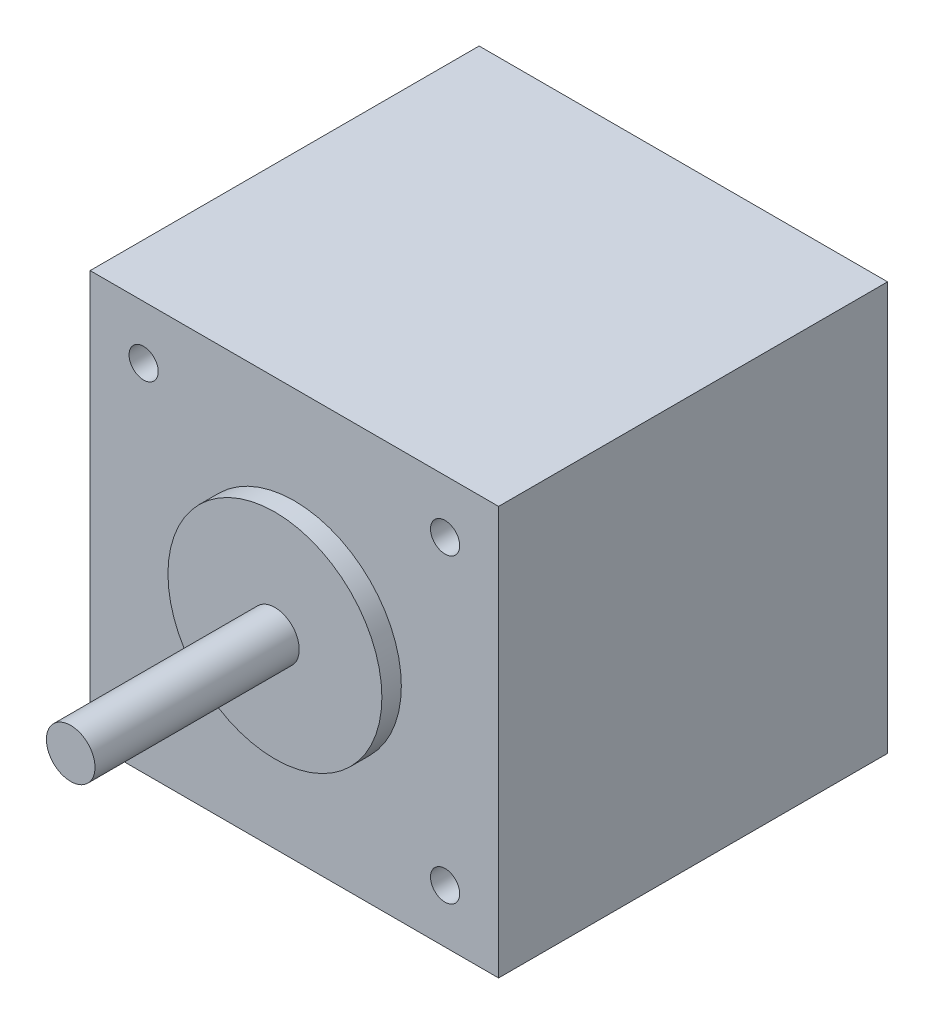
SolidWorks part; units mm, degrees
ref_plane "Спереди" through (0, 0, 0) normal (0, 0, 1) x (1, 0, 0)
ref_plane "Сверху" through (0, 0, 0) normal (0, 1, 0) x (1, 0, 0)
ref_plane "Справа" through (0, 0, 0) normal (1, 0, 0) x (0, 0, -1)
other "Configuration Table"
sketch "Эскиз1" plane through (0, 0, 0) normal (0, 0, 1) x (1, 0, 0)
  line L1 (-21, -21) -> (21, -21)
  line L2 (-21, -21) -> (-21, 21)
  line L3 (-21, 21) -> (21, 21)
  line L4 (21, -21) -> (21, 21)
  line L5 (-21, -21) -> (21, 21) construction
  line L6 (-21, 21) -> (21, -21) construction
  point P0 (0, 0)
  dimension "D1" = 42
  dimension "D2" = 42
extrude "Корпус" add sketch "Эскиз1" along normal blind 40
sketch "Эскиз2" plane through (0, 0, 0) normal (0, 0, 1) x (1, 0, 0)
  circle A0 centre (0, 0) radius 2.5
extrude "Вал_ПРЕДВ" add sketch "Эскиз2" along normal blind 63
sketch "Эскиз3" plane through (0, 0, 0) normal (0, 0, 1) x (1, 0, 0)
  circle A0 centre (0, 0) radius 11
  dimension "D1" = 22
extrude "Буртик_ПРЕДВ" add sketch "Эскиз3" along normal blind 42
sketch "Эскиз4" plane through (0, 0, 0) normal (0, 0, 1) x (1, 0, 0)
  circle A0 centre (-15.5, -15.5) radius 1.5
  circle A1 centre (-15.5, 15.5) radius 1.5
  circle A2 centre (15.5, -15.5) radius 1.5
  circle A3 centre (15.5, 15.5) radius 1.5
  dimension "D1" = 3
  dimension "D2" = 3
  dimension "D3" = 3
  dimension "D4" = 3
extrude "Крепеж_М3_ПРЕДВ" cut sketch "Эскиз4" against normal blind 4.5 from offset 40
equation "\"Мотор X ширина корпуса\"= 42.3"
equation "\"Мотор X высота корпуса\"= 42.3"
equation "\"Мотор X длина корпуса\"= 40"
equation "\"Мотор X вылет вала\"= 19.8"
equation "\"Мотор Y ширина корпуса\"= 42.3"
equation "\"Мотор Y высота корпуса\"= 42.3"
equation "\"Мотор Y длина корпуса\"= 48"
equation "\"Мотор Y вылет вала\"= 30"
equation "\"Мотор Z ширина корпуса\"= 42"
equation "\"Мотор Z высота корпуса\"= 42"
equation "\"Мотор Z длина корпуса\"= 40"
equation "\"Мотор Z вылет вала\"= 23"
equation "\"Мотор диаметр вала ПРЕДВ\"= 5"
equation "\"Мотор шаг крепления ПРЕДВ\"= 31"
equation "\"Мотор диаметр отверстий ПРЕДВ\"= 3"
equation "\"Мотор глубина отверстий ПРЕДВ\"= 4.5"
equation "\"Мотор диаметр буртика ПРЕДВ\"= 22"
equation "\"Мотор высота буртика ПРЕДВ\"= 2"
equation "\"Мотор диаметр шкива ПРЕДВ\"= 16"
equation "\"Мотор длина шкива ПРЕДВ\"= 12"
equation "\"Мотор отступ шкива ПРЕДВ\"= 5"
equation "\"Мотор X шаг градусов\"= 1.8"
equation "\"Мотор X ток А\"= 1.5"
equation "\"Мотор X сопротивление Ом\"= 1.3"
equation "\"Мотор X индуктивность мГн\"= 2"
equation "\"Мотор Y шаг градусов\"= 1.8"
equation "\"Мотор Y ток А\"= 2.2"
equation "\"Мотор Y сопротивление Ом\"= 0.9"
equation "\"Мотор Y индуктивность мГн\"= 2"
equation "\"Мотор Z шаг градусов\"= 1.8"
equation "\"Мотор Z ток А\"= 1"
equation "\"Мотор Z сопротивление Ом\"= 4"
equation "\"Мотор Z индуктивность мГн\"= 8"
equation "\"Мотор Y диаметр ротора\"= 25.78"
equation "\"D1@Эскиз1\" = \"Мотор Z ширина корпуса\""
equation "\"D2@Эскиз1\" = \"Мотор Z высота корпуса\""
equation "\"D1@Корпус\" = \"Мотор Z длина корпуса\""
equation "\"D1@Эскиз2\" = \"Мотор диаметр вала ПРЕДВ\""
equation "\"D1@Вал_ПРЕДВ\" = \"Мотор Z длина корпуса\" + \"Мотор Z вылет вала\""
equation "\"D1@Эскиз3\" = \"Мотор диаметр буртика ПРЕДВ\""
equation "\"D1@Буртик_ПРЕДВ\" = \"Мотор Z длина корпуса\" + \"Мотор высота буртика ПРЕДВ\""
equation "\"D1@Эскиз4\" = \"Мотор диаметр отверстий ПРЕДВ\""
equation "\"D2@Эскиз4\" = \"Мотор диаметр отверстий ПРЕДВ\""
equation "\"D3@Эскиз4\" = \"Мотор диаметр отверстий ПРЕДВ\""
equation "\"D4@Эскиз4\" = \"Мотор диаметр отверстий ПРЕДВ\""
equation "\"D1@Крепеж_М3_ПРЕДВ\" = \"Мотор глубина отверстий ПРЕДВ\""
equation "\"D19@Крепеж_М3_ПРЕДВ\" = \"Мотор Z длина корпуса\""
equation "\"Ширина груза\"= 420"
equation "\"Глубина груза\"= 490"
equation "\"Высота груза\"= 297"
equation "\"Ширина ячейки\"= \"Ширина груза\" + 10"
equation "\"Глубина ячейки\"= \"Глубина груза\" + 10"
equation "\"Высота ячейки\"= \"Высота груза\" + 10 + 13"
equation "\"Колво ячеек ширина\"= 2"
equation "\"Колво ячеек высота\"= 2"
equation "\"Толщина стенки\"= 10"
equation "\"Крепление дверцы\"= 5"
equation "\"Ширина рейки\"= \"Толщина шестерни\""
equation "\"Высота рейки\"= 20"
equation "\"Высота пола\"= 20"
equation "\"Колво полозьев\"= 5"
equation "\"Отступ рейки\"= 20"
equation "\"Глубина каретки\"= \"Глубина ячейки\" + 30 + \"Мотор Y высота корпуса\" + 20"
equation "\"Отступ шпильки\"= 26"
equation "\"Диаметр шпильки\"= 5"
equation "\"Длинна шпильки\"= ( \"Высота ячейки\" + \"Толщина стенки\" + \"Высота пола\" ) * \"Колво ячеек высота\" + ( \"Толщина стенки\" + \"Отступ рейки\" ) * 2 "
equation "\"Ширина пластины\"= 50  "
equation "\"Высота зона выгрузки\"= \"Высота ячейки\" * 2 + \"Толщина стенки\" * 2"
equation "\"Колво выгрузки\"= 1"
equation "\"Отступ крепления мотора фиксации\" = 30"
equation "\"Диаметр оси\"= 10"
equation "\"Диаметр ролика\"= 20"
equation "\"Колво роликов\"= 10"
equation "\"Шаг роликов\"= \"Диаметр ролика\" + 20"
equation "\"Ширина ячейки выгрузки\"= \"Ширина ячейки\" + \"Толщина стенки\" + \"Отступ крепления мотора фиксации\"*2"
equation "\"Длинна рейки\"= ( \"Ширина ячейки\" + \"Толщина стенки\" + \"Крепление дверцы\" ) * \"Колво ячеек ширина\" + \"Ширина ячейки выгрузки\" * \"Колво выгрузки\" + \"Толщина стенки\""
